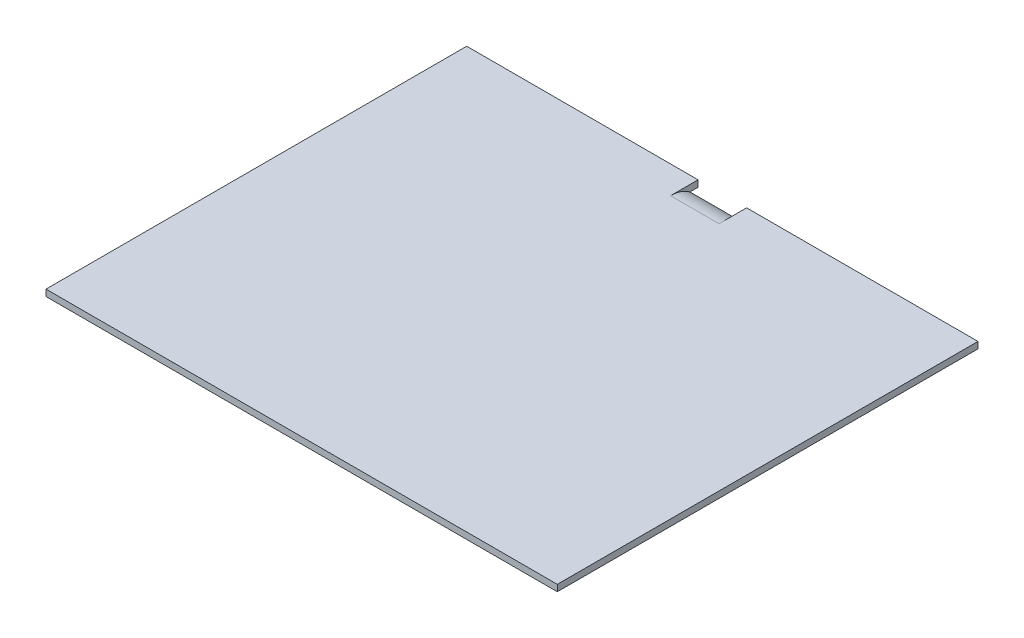
SolidWorks part; units mm, degrees
ref_plane "Plan de face" through (0, 0, 0) normal (0, 0, 1) x (1, 0, 0)
ref_plane "Plan de dessus" through (0, 0, 0) normal (0, 1, 0) x (1, 0, 0)
ref_plane "Plan de droite" through (0, 0, 0) normal (1, 0, 0) x (0, 0, -1)
sketch "Esquisse1" plane through (0, 0, 0) normal (0, 1, 0) x (1, 0, 0)
  line L1 (-39.5, 32.5) -> (39.5, 32.5)
  line L2 (-39.5, 32.5) -> (-39.5, -32.5)
  line L3 (-39.5, -32.5) -> (39.5, -32.5)
  line L4 (39.5, 32.5) -> (39.5, -32.5)
  line L5 (-39.5, 32.5) -> (39.5, -32.5) construction
  line L6 (-39.5, -32.5) -> (39.5, 32.5) construction
  point P0 (0, 0)
  dimension "D1" = 79
  dimension "D2" = 65
extrude "Boss.-Extru.1" add sketch "Esquisse1" along normal blind 1
ref_plane "Plan1" through (39.5, 1, 32.5) normal (0, -1, 0) x (-1, 0, 0)
sketch "Esquisse3" plane through (0, 0, -32.5) normal (0, 0, -1) x (-1, 0, 0)
  line L0 (-39.5, 0.5) -> (39.5, 0.5) construction
  line L1 (-39.5, 1) -> (-39.5, 0) construction
  line L2 (39.5, 1) -> (39.5, 0) construction
  line L3 (0, 1) -> (0, 0) construction
  line L4 (-39.5, 1) -> (39.5, 1) construction
  line L6 (-3.75, 4.25) -> (3.75, 4.25)
  line L7 (-3.75, 4.25) -> (-3.75, -3.25)
  line L8 (-3.75, -3.25) -> (3.75, -3.25)
  line L9 (3.75, 4.25) -> (3.75, -3.25)
  line L10 (-3.75, 4.25) -> (3.75, -3.25) construction
  line L11 (-3.75, -3.25) -> (3.75, 4.25) construction
  point P11 (0, 0.5)
  dimension "D1" = 7.5
  dimension "D2" = 7.5
extrude "Enlèv. mat.-Extru.1" cut sketch "Esquisse3" against normal blind 1.25
fillet "Congé1" radius 5 1 edges at (0, 1, -31.25)
